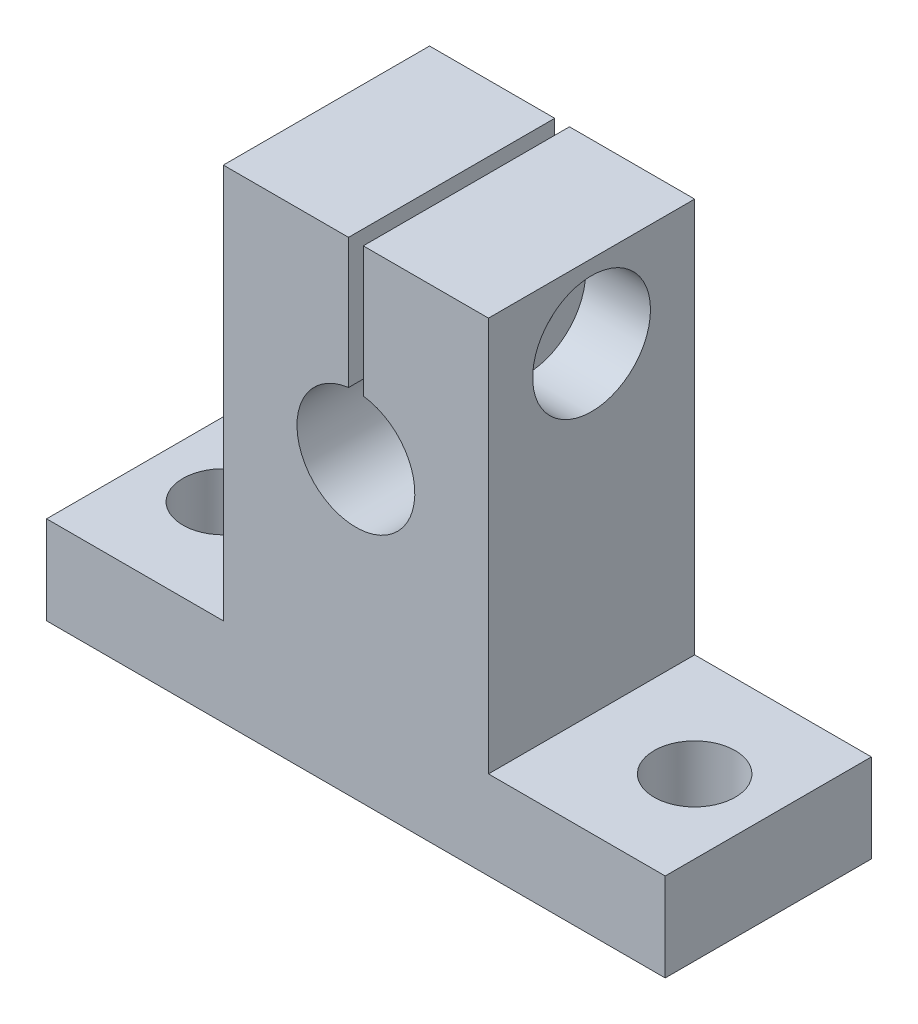
SolidWorks part; units mm, degrees
ref_plane "Front Plane" through (0, 0, 0) normal (0, 0, 1) x (1, 0, 0)
ref_plane "Top Plane" through (0, 0, 0) normal (0, 1, 0) x (1, 0, 0)
ref_plane "Right Plane" through (0, 0, 0) normal (1, 0, 0) x (0, 0, -1)
sketch "Croquis1" plane through (0, 0, 0) normal (0, 0, 1) x (1, 0, 0)
  line L0 (-21, 0) -> (21, 0)
  line L1 (21, 0) -> (21, 6)
  line L2 (21, 6) -> (9, 6)
  line L3 (9, 6) -> (9, 32.8)
  line L4 (9, 32.8) -> (-9, 32.8)
  line L5 (-9, 32.8) -> (-9, 6)
  line L6 (-9, 6) -> (-21, 6)
  line L7 (-21, 6) -> (-21, 0)
  circle A0 centre (0, 20) radius 4
  point P3 (0, 32.8)
  dimension "D5" = 8
  dimension "D1" = 6
  dimension "D2" = 42
  dimension "D3" = 32.8
  dimension "D4" = 18
  dimension "D6" = 20
extrude "Saliente-Extruir1" add sketch "Croquis1" along normal blind 7 and the other way blind 7
hole_wizard "Taladro de margen para M51" positions "Croquis3" profile "Croquis4" hole size "M5" standard "DIN" end condition through all
sketch "Croquis3" plane through (0, 0, 0) normal (0, -1, 0) x (-1, 0, 0)
  line L0 (-16, 0) -> (16, 0) construction
  point P1 (-16, 0)
  point P2 (16, 0)
  dimension "D1" = 32
sketch "Croquis4" plane through (16, 0, 0) normal (1, 0, 0) x (0, 0, -1)
  line L0 (0, 0) -> (0, 32.8)
  line L1 (0, 32.8) -> (2.75, 32.8)
  line L2 (2.75, 32.8) -> (2.75, 0)
  line L5 (2.75, 0) -> (0, 0)
  line L11 (0, -6.35) -> (0, 107.95) construction
  dimension "Diámetro de taladro hasta el siguiente" = 5.5
  dimension "Profundidad de taladro hasta el siguiente" = 32.8
sketch "Croquis6" plane through (0, 0, 0) normal (0, 0, 1) x (1, 0, 0)
  line L1 (-0.5, 37.8486) -> (0.5, 37.8486)
  line L2 (-0.5, 37.8486) -> (-0.5, 20)
  line L3 (-0.5, 20) -> (0.5, 20)
  line L4 (0.5, 37.8486) -> (0.5, 20)
  line L5 (-0.5, 37.8486) -> (0.5, 20) construction
  line L6 (-0.5, 20) -> (0.5, 37.8486) construction
  point P0 (0, 28.9243)
  dimension "D1" = 20
  dimension "D2" = 1
extrude "Cortar-Extruir1" cut sketch "Croquis6" against normal through all and the other way through all
hole_wizard "Refrentado para tornillo con cabeza hueca de M41" positions "Croquis7" profile "Croquis8" counterbore size "M4" standard "DIN" end condition through all
sketch "Croquis7" plane through (9, 0, 0) normal (1, 0, 0) x (0, 0, -1)
  line L0 (7, 32.8) -> (-7, 32.8) construction
  point P4 (0, 27.8)
  dimension "D1" = 5
sketch "Croquis8" plane through (9, 27.8, 0) normal (0, 1, 0) x (0, 0, -1)
  line L0 (0, 0) -> (0, 30)
  line L1 (0, 30) -> (2.25, 30)
  line L3 (2.25, 30) -> (2.25, 4.4)
  line L4 (2.25, 4.4) -> (4, 4.4)
  line L5 (4, 4.4) -> (4, 0)
  line L7 (4, 0) -> (0, 0)
  line L11 (0, -6.35) -> (0, 107.95) construction
  dimension "Diámetro de taladro hasta el siguiente" = 4.5
  dimension "Profundidad de taladro hasta el siguiente" = 30
  dimension "Diámetro de refrentado" = 8
  dimension "Profundidad de refrentado" = 4.4
